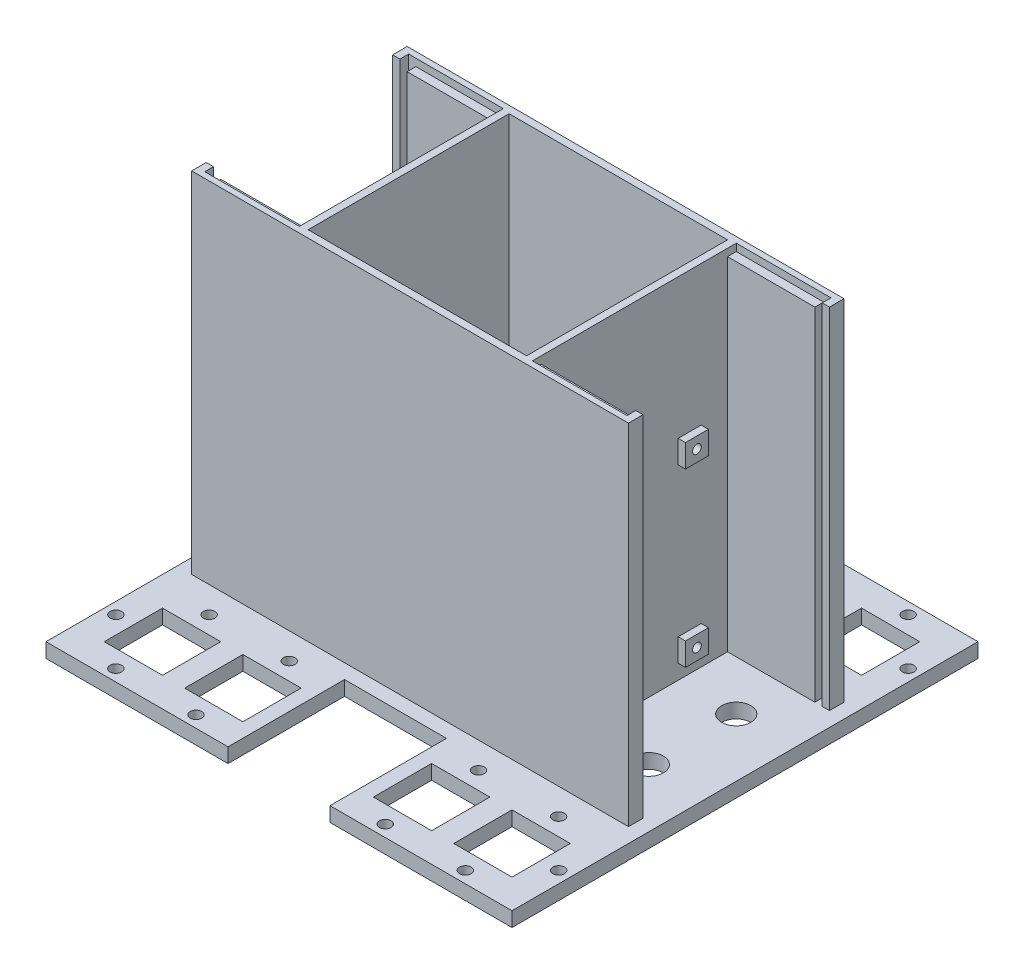
SolidWorks part; units mm, degrees
material "PPE"
ref_plane "Front Plane" through (0, 0, 0) normal (0, 0, 1) x (1, 0, 0)
ref_plane "Top Plane" through (0, 0, 0) normal (0, 1, 0) x (1, 0, 0)
ref_plane "Right Plane" through (0, 0, 0) normal (1, 0, 0) x (0, 0, -1)
sketch "Sketch1" plane through (0, 0, 0) normal (0, 1, 0) x (1, 0, 0)
  line L1 (-101.6, -101.6) -> (101.6, -101.6)
  line L2 (-101.6, -101.6) -> (-101.6, 101.6)
  line L3 (-101.6, 101.6) -> (101.6, 101.6)
  line L4 (101.6, -101.6) -> (101.6, 101.6)
  line L5 (-101.6, -101.6) -> (101.6, 101.6) construction
  line L6 (-101.6, 101.6) -> (101.6, -101.6) construction
  point P0 (0, 0)
  dimension "D1" = 203.2
  dimension "D2" = 203.2
extrude "Boss-Extrude1" add sketch "Sketch1" along normal blind 6.35
sketch "Sketch2" plane through (0, 6.35, 0) normal (0, 1, 0) x (1, 0, 0)
  line L0 (0, 0) -> (0, 106.1242) construction
  line L7 (-22.225, 101.6) -> (22.225, 101.6)
  line L8 (-22.225, 101.6) -> (-22.225, 55.88)
  line L9 (-22.225, 55.88) -> (22.225, 55.88)
  line L10 (22.225, 101.6) -> (22.225, 55.88)
  line L11 (-22.225, 101.6) -> (22.225, 55.88) construction
  line L12 (-22.225, 55.88) -> (22.225, 101.6) construction
  line L13 (101.6, 101.6) -> (-101.6, 101.6) construction
  line L14 (-101.6, -101.6) -> (101.6, -101.6) construction
  line L15 (-22.225, -101.6) -> (22.225, -101.6)
  line L16 (-22.225, -101.6) -> (-22.225, -50.8)
  line L17 (-22.225, -50.8) -> (22.225, -50.8)
  line L18 (22.225, -101.6) -> (22.225, -50.8)
  line L19 (-22.225, -101.6) -> (22.225, -50.8) construction
  line L20 (-22.225, -50.8) -> (22.225, -101.6) construction
  point P5 (0, 78.74)
  point P18 (0, -76.2)
  dimension "D3" = 44.45
  dimension "D4" = 45.72
  dimension "D5" = 44.45
  dimension "D6" = 50.8
extrude "Cut-Extrude1" cut sketch "Sketch2" against normal through all
sketch "Sketch3" plane through (0, 6.35, 0) normal (0, 1, 0) x (1, 0, 0)
  line L0 (-22.225, 101.6) -> (-101.6, 101.6) construction
  line L1 (-53.848, 88.9) -> (-28.448, 88.9)
  line L2 (-53.848, 88.9) -> (-53.848, 63.5)
  line L3 (-53.848, 63.5) -> (-28.448, 63.5)
  line L4 (-28.448, 88.9) -> (-28.448, 63.5)
  line L5 (-53.848, 88.9) -> (-28.448, 63.5) construction
  line L6 (-53.848, 63.5) -> (-28.448, 88.9) construction
  line L7 (-22.225, 101.6) -> (-22.225, 55.88) construction
  line L8 (-41.148, 76.2) -> (28.1634, 76.2) construction
  line L9 (-88.9, 63.5) -> (-63.5, 63.5)
  line L10 (-88.9, 63.5) -> (-88.9, 88.9)
  line L11 (-88.9, 88.9) -> (-63.5, 88.9)
  line L12 (-63.5, 63.5) -> (-63.5, 88.9)
  line L13 (-88.9, 63.5) -> (-63.5, 88.9) construction
  line L14 (-88.9, 88.9) -> (-63.5, 63.5) construction
  line L16 (-76.2, 96.52) -> (-16.3872, 96.52) construction
  circle A0 centre (-96.52, 76.2) radius 2.54
  circle A1 centre (-76.2, 96.52) radius 2.54
  circle A2 centre (-55.88, 76.2) radius 2.54 [skipped]
  circle A3 centre (-76.2, 55.88) radius 2.54
  circle A4 centre (-41.275, 96.52) radius 2.54
  circle A5 centre (-41.275, 55.88) radius 2.54
  point P0 (-41.148, 76.2)
  point P9 (-76.2, 76.2)
  point P27 (-76.2, 76.2)
  dimension "D8" = 5.08
  dimension "D11" = 5.08
  dimension "D1" = 25.4
  dimension "D2" = 25.4
  dimension "D3" = 12.7
  dimension "D4" = 6.223
  dimension "D5" = 25.4
  dimension "D6" = 25.4
  dimension "D7" = 9.652
  dimension "D9" = 7.62
  dimension "D12" = 34.925
  dimension "D10" = 4
extrude "Cut-Extrude2" cut sketch "Sketch3" against normal blind 6.35
mirror "Mirror1" about plane through (0, 0, 0) normal (1, 0, 0) of "Cut-Extrude2"
mirror "Mirror2" about plane through (0, 0, 0) normal (0, 0, 1) of "Mirror1"
sketch "Sketch4" plane through (0, 6.35, 0) normal (0, 1, 0) x (1, 0, 0)
  line L5 (101.6, -101.6) -> (101.6, 101.6) construction
  line L6 (-50.8, -44.45) -> (50.8, -44.45)
  line L8 (-50.8, -44.45) -> (-50.8, 49.53)
  line L9 (-50.8, 49.53) -> (50.8, 49.53)
  line L10 (50.8, -44.45) -> (50.8, 49.53)
  line L11 (-101.6, 101.6) -> (-101.6, -101.6) construction
  line L12 (-22.225, 55.88) -> (22.225, 55.88) construction
  line L13 (22.225, -50.8) -> (-22.225, -50.8) construction
  line L15 (-47.625, -41.275) -> (47.625, -41.275)
  line L16 (-47.625, -41.275) -> (-47.625, 46.355)
  line L17 (-47.625, 46.355) -> (47.625, 46.355)
  line L18 (47.625, -41.275) -> (47.625, 46.355)
  point P0 (0, 0)
  dimension "D1" = 50.8
  dimension "D2" = 50.8
  dimension "D3" = 6.35
  dimension "D4" = 6.35
  dimension "D5" = 3.175
  dimension "D6" = 3.175
  dimension "D7" = 3.175
  dimension "D8" = 3.175
extrude "Boss-Extrude2" add sketch "Sketch4" along normal blind 152.4
sketch "Sketch5" plane through (50.8, 0, 0) normal (1, 0, 0) x (0, 0, -1)
  line L5 (2.54, 158.75) -> (2.54, -3.612) construction
  line L6 (-44.45, 158.75) -> (49.53, 158.75) construction
  line L12 (-24.13, 107.95) -> (29.21, 107.95) construction
  line L13 (-44.45, 6.35) -> (49.53, 6.35) construction
  line L14 (29.21, 107.95) -> (29.21, 6.35) construction
  line L15 (-24.13, 107.95) -> (-24.13, 6.35) construction
  line L17 (-26.59, 88.98) -> (-16.59, 88.98)
  line L18 (-26.59, 88.98) -> (-26.59, 98.98)
  line L19 (-26.59, 98.98) -> (-16.59, 98.98)
  line L20 (-16.59, 88.98) -> (-16.59, 98.98)
  line L21 (-26.59, 88.98) -> (-16.59, 98.98) construction
  line L22 (-26.59, 98.98) -> (-16.59, 88.98) construction
  line L23 (21.67, 87.71) -> (31.67, 87.71)
  line L24 (21.67, 87.71) -> (21.67, 97.71)
  line L25 (21.67, 97.71) -> (31.67, 97.71)
  line L26 (31.67, 87.71) -> (31.67, 97.71)
  line L27 (21.67, 87.71) -> (31.67, 97.71) construction
  line L28 (21.67, 97.71) -> (31.67, 87.71) construction
  line L29 (-26.59, 6.43) -> (-16.59, 6.43)
  line L30 (-26.59, 6.43) -> (-26.59, 16.43)
  line L31 (-26.59, 16.43) -> (-16.59, 16.43)
  line L32 (-16.59, 6.43) -> (-16.59, 16.43)
  line L33 (-26.59, 6.43) -> (-16.59, 16.43) construction
  line L34 (-26.59, 16.43) -> (-16.59, 6.43) construction
  line L35 (21.67, 12.78) -> (31.67, 12.78)
  line L36 (21.67, 12.78) -> (21.67, 22.78)
  line L37 (21.67, 22.78) -> (31.67, 22.78)
  line L38 (31.67, 12.78) -> (31.67, 22.78)
  line L39 (21.67, 12.78) -> (31.67, 22.78) construction
  line L40 (21.67, 22.78) -> (31.67, 12.78) construction
  circle A0 centre (-21.59, 93.98) radius 1.6
  circle A1 centre (26.67, 92.71) radius 1.6
  circle A2 centre (26.67, 17.78) radius 1.6
  circle A3 centre (-21.59, 11.43) radius 1.6
  point P2 (2.54, 107.95)
  dimension "D3" = 3.2
  dimension "D6" = 3.2
  dimension "D9" = 3.2
  dimension "D12" = 3.2
  dimension "D1" = 53.34
  dimension "D2" = 101.6
  dimension "D4" = 2.54
  dimension "D5" = 13.97
  dimension "D7" = 2.54
  dimension "D8" = 15.24
  dimension "D10" = 2.54
  dimension "D11" = 90.17
  dimension "D13" = 2.54
  dimension "D14" = 96.52
  dimension "D15" = 10
  dimension "D16" = 10
  dimension "D17" = 10
  dimension "D18" = 10
  dimension "D19" = 10
  dimension "D20" = 10
  dimension "D21" = 10
  dimension "D22" = 10
extrude "Boss-Extrude3" add sketch "Sketch5" along normal blind 3.175
ref_plane "Plane1" through (53.975, 0, 0) normal (1, 0, 0) x (0, 0, -1)
sketch "Sketch8" plane through (53.975, 0, 0) normal (1, 0, 0) x (0, 0, -1)
  circle A0 centre (-21.59, 93.98) radius 1.905
  circle A1 centre (26.67, 92.71) radius 1.905
  circle A2 centre (-21.59, 11.43) radius 1.905
  circle A3 centre (26.67, 17.78) radius 1.905
  dimension "D1" = 3.81
  dimension "D2" = 3.81
  dimension "D3" = 3.81
  dimension "D4" = 3.81
extrude "Cut-Extrude3" cut sketch "Sketch8" against normal up to next
sketch "Sketch9" plane through (50.8, 0, 0) normal (1, 0, 0) x (0, 0, -1)
  line L0 (-44.45, 158.75) -> (49.53, 158.75) construction
  line L1 (-44.45, 6.35) -> (-38.1, 6.35)
  line L2 (-44.45, 6.35) -> (-44.45, 158.75)
  line L3 (-44.45, 158.75) -> (-38.1, 158.75)
  line L4 (-38.1, 6.35) -> (-38.1, 158.75)
  line L6 (49.53, 6.35) -> (43.18, 6.35)
  line L7 (49.53, 6.35) -> (49.53, 158.75)
  line L8 (49.53, 158.75) -> (43.18, 158.75)
  line L9 (43.18, 6.35) -> (43.18, 158.75)
  dimension "D1" = 6.35
  dimension "D2" = 6.35
extrude "Boss-Extrude4" add sketch "Sketch9" along normal blind 44.45
sketch "Sketch12" plane through (0, 158.75, 0) normal (0, 1, 0) x (1, 0, 0)
  line L0 (95.25, -38.1) -> (50.8, -38.1) construction
  line L1 (92.075, -38.1) -> (88.9, -38.1)
  line L2 (92.075, -38.1) -> (92.075, -41.91)
  line L3 (92.075, -41.91) -> (88.9, -41.91)
  line L4 (88.9, -38.1) -> (88.9, -41.91)
  line L5 (95.25, -38.1) -> (95.25, -44.45) construction
  dimension "D1" = 3.175
  dimension "D2" = 3.175
  dimension "D3" = 3.81
extrude "Cut-Extrude4" cut sketch "Sketch12" against normal up to surface (152.4 mm away) up to face at (-41.148, 6.35, 76.2)
ref_plane "Plane2" through (0, 0, -2.54) normal (0, 0, -1) x (-1, 0, 0)
sketch "Sketch13" plane through (0, 158.75, 0) normal (0, 1, 0) x (1, 0, 0)
  line L1 (88.9, -41.91) -> (50.8, -41.91)
  line L2 (88.9, -41.91) -> (88.9, -38.1)
  line L3 (88.9, -38.1) -> (50.8, -38.1)
  line L4 (50.8, -41.91) -> (50.8, -38.1)
  line L6 (88.9, -38.1) -> (88.9, -41.91) construction
  dimension "D1" = 3.81
extrude "Cut-Extrude5" cut sketch "Sketch13" against normal blind 3.175
mirror "Mirror3" about plane through (0, 0, -2.54) normal (0, 0, -1) of "Cut-Extrude5", "Cut-Extrude4"
sketch "Sketch14" plane through (-50.8, 0, 0) normal (-1, 0, 0) x (0, 0, 1)
  line L0 (-49.53, 158.75) -> (44.45, 158.75) construction
  line L1 (-49.53, 6.35) -> (-43.18, 6.35)
  line L2 (-49.53, 6.35) -> (-49.53, 158.75)
  line L3 (-49.53, 158.75) -> (-43.18, 158.75)
  line L4 (-43.18, 6.35) -> (-43.18, 158.75)
  line L6 (44.45, 6.35) -> (38.1, 6.35)
  line L7 (44.45, 6.35) -> (44.45, 158.75)
  line L8 (44.45, 158.75) -> (38.1, 158.75)
  line L9 (38.1, 6.35) -> (38.1, 158.75)
  dimension "D1" = 6.35
  dimension "D2" = 6.35
extrude "Boss-Extrude5" add sketch "Sketch14" along normal blind 44.45
sketch "Sketch15" plane through (0, 158.75, 0) normal (0, 1, 0) x (1, 0, 0)
  line L0 (-95.25, -38.1) -> (-50.8, -38.1) construction
  line L1 (-92.075, -38.1) -> (-88.9, -38.1)
  line L2 (-92.075, -38.1) -> (-92.075, -41.91)
  line L3 (-92.075, -41.91) -> (-88.9, -41.91)
  line L4 (-88.9, -38.1) -> (-88.9, -41.91)
  line L5 (-95.25, -44.45) -> (-95.25, -38.1) construction
  point P6 (-92.075, -40.005)
  dimension "D1" = 3.175
  dimension "D2" = 3.175
  dimension "D3" = 3.81
extrude "Cut-Extrude6" cut sketch "Sketch15" against normal blind 152.4
sketch "Sketch16" plane through (0, 158.75, 0) normal (0, 1, 0) x (1, 0, 0)
  line L0 (-95.25, -44.45) -> (95.25, -44.45) construction
  line L1 (-88.9, -38.1) -> (-50.8, -38.1)
  line L2 (-88.9, -38.1) -> (-88.9, -41.91)
  line L3 (-88.9, -41.91) -> (-50.8, -41.91)
  line L4 (-50.8, -38.1) -> (-50.8, -41.91)
  line L5 (-50.8, 43.18) -> (-50.8, -38.1) construction
  dimension "D1" = 2.54
extrude "Cut-Extrude7" cut sketch "Sketch16" against normal blind 3.175
mirror "Mirror4" about plane through (0, 0, -2.54) normal (0, 0, -1) of "Cut-Extrude6", "Cut-Extrude7"
sketch "Sketch17" plane through (0, 6.35, 0) normal (0, 1, 0) x (1, 0, 0)
  line L0 (-50.8, 2.54) -> (114.4914, 2.54) construction
  line L1 (-47.625, -41.275) -> (47.625, -41.275) construction
  line L3 (-50.8, 43.18) -> (-50.8, -38.1) construction
  line L7 (-88.9, 43.18) -> (-88.9, -38.1) construction
  line L9 (47.625, 46.355) -> (-47.625, 46.355) construction
  line L10 (-47.625, 46.355) -> (-47.625, -41.275) construction
  line L11 (47.625, -41.275) -> (47.625, 46.355) construction
  circle A0 centre (-76.2, -16.51) radius 6.35
  circle A1 centre (-76.2, 21.59) radius 6.35
  circle A2 centre (-28.575, 27.305) radius 6.35
  circle A3 centre (28.575, -22.225) radius 6.35
  dimension "D1" = 12.7
  dimension "D2" = 12.7
  dimension "D4" = 12.7
  dimension "D6" = 19.05
  dimension "D7" = 12.7
  dimension "D8" = 19.05
  dimension "D9" = 19.05
  dimension "D3" = 19.05
  dimension "D5" = 19.05
extrude "Cut-Extrude8" cut sketch "Sketch17" against normal up to next
mirror "Mirror5" about plane through (0, 0, 0) normal (1, 0, 0) of face at (-76.2, 0, 10.16) of face at (-76.2, 0, -27.94)
scale "Scale1" [suppressed]
